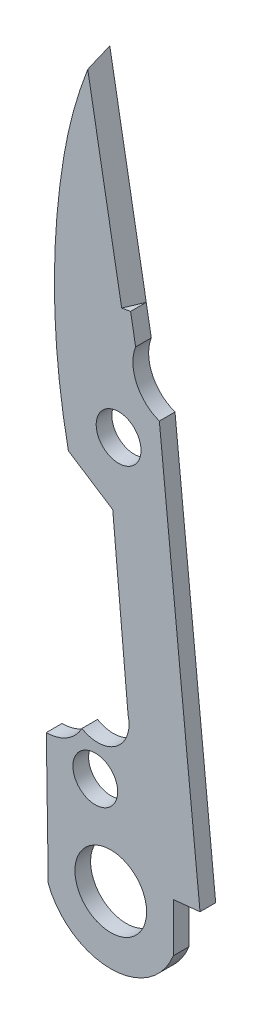
SolidWorks part; units mm, degrees
material "AISI 4340 Steel, normalized"
ref_plane "Front Plane" through (0, 0, 0) normal (0, 0, 1) x (1, 0, 0)
ref_plane "Top Plane" through (0, 0, 0) normal (0, 1, 0) x (1, 0, 0)
ref_plane "Right Plane" through (0, 0, 0) normal (1, 0, 0) x (0, 0, -1)
sketch "Sketch1" plane through (0, 0, 0) normal (0, 0, 1) x (1, 0, 0)
  line L0 (16.7881, 37.7732) -> (83.9405, 37.7732) construction
  line L1 (54.2123, 59.4194) -> (56.5636, 46.2645)
  line L2 (57.9078, 43.2984) -> (60.2136, 20.3565)
  line L3 (60.2136, 20.3565) -> (58.6972, 20.2041)
  line L4 (58.6972, 20.2041) -> (58.6972, 17.4355)
  line L5 (51.5002, 24.8015) -> (51.6106, 17.4355)
  line L6 (52.752, 39.2541) -> (55.2654, 37.6285)
  line L7 (55.2654, 37.6285) -> (56.1361, 27.9754)
  line L8 (65.5217, 55.4749) -> (66.0485, 55.2911) construction
  line L9 (54.6075, 45.2908) -> (58.958, 57.7642) construction
  arc A0 (52.4996, 53.6305) -> (52.752, 39.2541) centre (91.3279, 47.1219) ccw
  arc A1 (52.4996, 53.6305) -> (54.2123, 59.4194) centre (77.0491, 49.5154) cw
  arc A2 (56.5636, 46.2645) -> (57.9078, 43.2984) centre (58.6972, 45.4438) ccw
  arc A3 (51.6106, 17.4355) -> (58.6972, 17.4355) centre (55.1539, 18.8359) ccw
  arc A4 (56.1361, 27.9754) -> (53.5156, 26.0086) centre (54.411, 27.5447) cw
  arc A5 (53.5156, 26.0086) -> (51.5002, 24.8015) centre (51.5002, 27.0875) cw
  circle A6 centre (55.5984, 41.3369) radius 1.27
  circle A7 centre (54.2776, 23.9125) radius 1.27
  dimension "D1" = 2.54
  dimension "D3" = 3.81
  dimension "D7" = 39.37
  dimension "D12" = 2.286
  dimension "D13" = 1.778
  dimension "D29" = 2.286
  dimension "D30" = 17.4244
  dimension "D31" = 1.3208
  dimension "D5" = 24.892
  dimension "D2" = 8.6458
  dimension "D4" = 1.524
  dimension "D6" = 0.585
  dimension "D9" = 2.9933
  dimension "D10" = 9.6531
  dimension "D11" = 7.366
  dimension "D14" = 6.477
  dimension "D15" = 2.667
  dimension "D16" = 4.4196
  dimension "D17" = 6.477
  dimension "D18" = 3.7084
  dimension "D19" = 3.556
  dimension "D20" = 3.175
  dimension "D21" = 3.6322
  dimension "D22" = 0.762
  dimension "D23" = 13.716
  dimension "D24" = 15.3416
  dimension "D25" = 29.718
  dimension "D26" = 1.778
  dimension "D27" = 22.352
  dimension "D28" = 2.286
extrude "Boss-Extrude3" add sketch "Sketch1" along normal blind 0.889
sketch "Sketch3" plane through (0, 0, 0.889) normal (0, 0, 1) x (1, 0, 0)
  circle A0 centre (55.1539, 18.8359) radius 2.032
  dimension "D1" = 4.064
extrude "Cut-Extrude1" cut sketch "Sketch3" against normal through all
ref_plane "Plane2" through (-10.5709, 59.1404, 0) normal (-0.176, 0.9844, 0) x (0.9844, 0.176, 0)
sketch "Sketch4" plane through (-10.5709, 59.1404, 0) normal (-0.176, 0.9844, 0) x (0.9844, 0.176, 0)
  line L5 (63.8215, 0) -> (63.8215, -0.889)
  line L7 (61.117, -0.889) -> (63.8215, -0.889) construction
  line L8 (63.3083, -0.889) -> (63.8215, -0.889)
  line L9 (63.3083, -0.889) -> (63.8215, 0)
  dimension "D1" = 30
extrude "Cut-Extrude2" cut sketch "Sketch4" against normal blind 22.86
